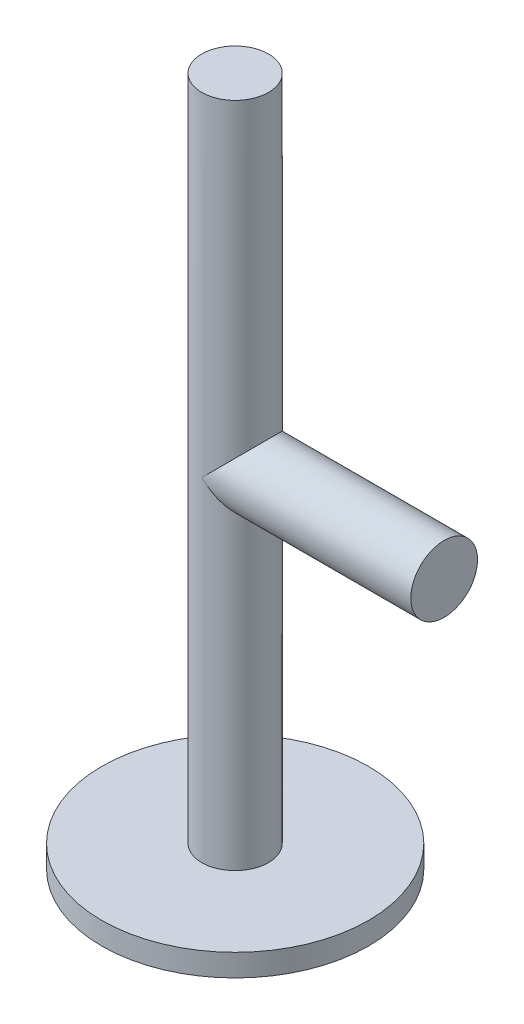
SolidWorks part; units mm, degrees
ref_plane "Front Plane" through (0, 0, 0) normal (0, 0, 1) x (1, 0, 0)
ref_plane "Top Plane" through (0, 0, 0) normal (0, 1, 0) x (1, 0, 0)
ref_plane "Right Plane" through (0, 0, 0) normal (1, 0, 0) x (0, 0, -1)
sketch "Sketch1" plane through (0, 0, 0) normal (0, 1, 0) x (1, 0, 0)
  circle A0 centre (0, 0) radius 7.5
  dimension "D1" = 15
extrude "Boss-Extrude1" add sketch "Sketch1" along normal blind 150
sketch "Sketch2" plane through (0, 0, 0) normal (0, -1, 0) x (1, 0, 0)
  circle A0 centre (0, 0) radius 30
  dimension "D1" = 60
extrude "Boss-Extrude2" add sketch "Sketch2" along normal blind 5 contours A0
sketch "Sketch5" plane through (0, 0, 0) normal (1, 0, 0) x (0, 0, -1)
  circle A0 centre (0, 75) radius 7.5
  dimension "D1" = 15
extrude "Boss-Extrude3" add sketch "Sketch5" along normal blind 47
